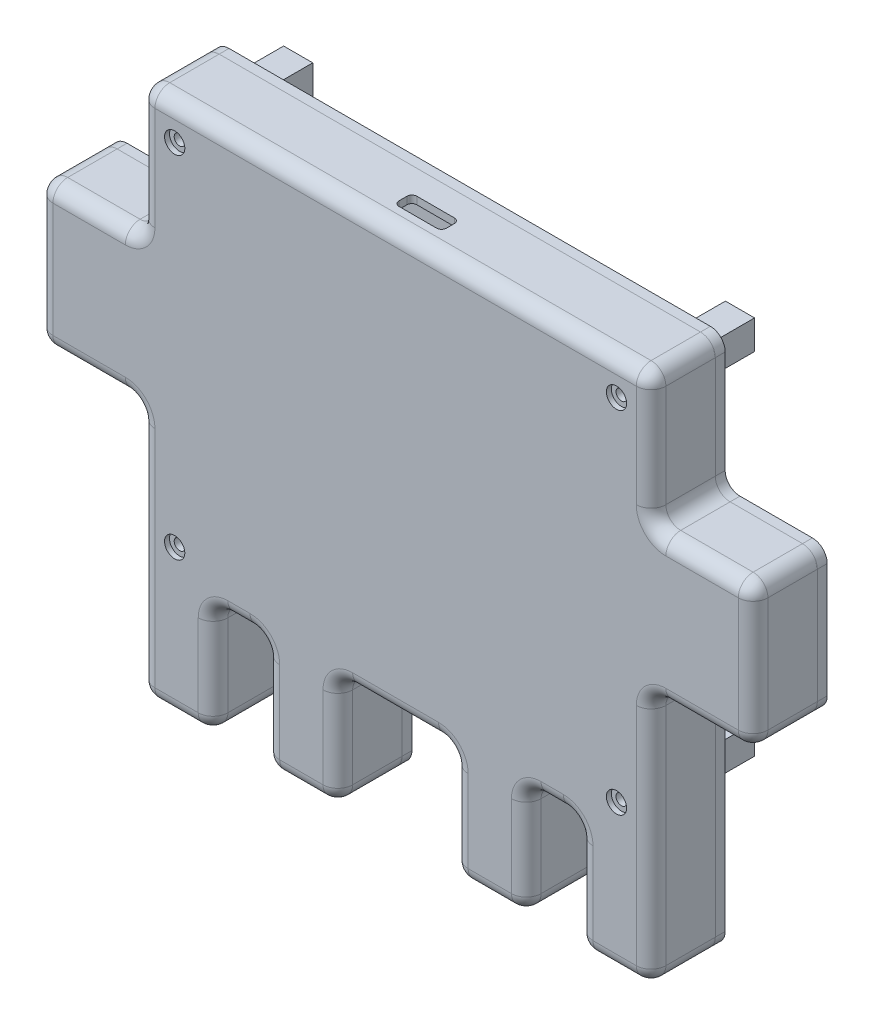
SolidWorks part; units mm, degrees
ref_plane "Front Plane" through (0, 0, 0) normal (0, 0, 1) x (1, 0, 0)
ref_plane "Top Plane" through (0, 0, 0) normal (0, 1, 0) x (1, 0, 0)
ref_plane "Right Plane" through (0, 0, 0) normal (1, 0, 0) x (0, 0, -1)
sketch "圖片" plane through (0, 0, 0) normal (0, 0, 1) x (1, 0, 0)
  line L0 (219.174, 501.4094) -> (1128.5073, 501.4094) construction
sketch "padTop" plane through (0, 0, 0) normal (0, 0, 1) x (1, 0, 0)
  line L0 (36.7115, 8.5135) -> (50.8115, 8.5135)
  line L1 (36.7115, 27.6135) -> (50.8115, 27.6135)
  line L2 (36.7115, 27.6135) -> (36.7115, 13.5135)
  line L3 (36.7115, 13.5135) -> (50.8115, 13.5135)
  line L4 (50.8115, 27.6135) -> (50.8115, 13.5135)
  line L5 (36.7115, 27.6135) -> (50.8115, 13.5135) construction
  line L6 (36.7115, 13.5135) -> (50.8115, 27.6135) construction
  line L7 (36.7115, 8.5135) -> (36.7115, -5.5865)
  line L8 (36.7115, -5.5865) -> (50.8115, -5.5865)
  line L9 (50.8115, 8.5135) -> (50.8115, -5.5865)
  line L10 (36.7115, 8.5135) -> (50.8115, -5.5865) construction
  line L11 (36.7115, -5.5865) -> (50.8115, 8.5135) construction
  line L12 (94.0115, 8.5135) -> (108.1115, 8.5135)
  line L13 (94.0115, 27.6135) -> (108.1115, 27.6135)
  line L14 (94.0115, 27.6135) -> (94.0115, 13.5135)
  line L15 (94.0115, 13.5135) -> (108.1115, 13.5135)
  line L16 (108.1115, 27.6135) -> (108.1115, 13.5135)
  line L17 (94.0115, 27.6135) -> (108.1115, 13.5135) construction
  line L18 (94.0115, 13.5135) -> (108.1115, 27.6135) construction
  line L19 (94.0115, 8.5135) -> (94.0115, -5.5865)
  line L20 (94.0115, -5.5865) -> (108.1115, -5.5865)
  line L21 (108.1115, 8.5135) -> (108.1115, -5.5865)
  line L22 (94.0115, 8.5135) -> (108.1115, -5.5865) construction
  line L23 (94.0115, -5.5865) -> (108.1115, 8.5135) construction
  line L24 (55.8115, 8.5135) -> (69.9115, 8.5135)
  line L25 (55.8115, 27.6135) -> (69.9115, 27.6135)
  line L26 (55.8115, 27.6135) -> (55.8115, 13.5135)
  line L27 (55.8115, 13.5135) -> (69.9115, 13.5135)
  line L28 (69.9115, 27.6135) -> (69.9115, 13.5135)
  line L29 (55.8115, 27.6135) -> (69.9115, 13.5135) construction
  line L30 (55.8115, 13.5135) -> (69.9115, 27.6135) construction
  line L31 (55.8115, 8.5135) -> (55.8115, -5.5865)
  line L32 (55.8115, -5.5865) -> (69.9115, -5.5865)
  line L33 (69.9115, 8.5135) -> (69.9115, -5.5865)
  line L34 (55.8115, 8.5135) -> (69.9115, -5.5865) construction
  line L35 (55.8115, -5.5865) -> (69.9115, 8.5135) construction
  line L36 (74.9115, 8.5135) -> (89.0115, 8.5135)
  line L37 (74.9115, 27.6135) -> (89.0115, 27.6135)
  line L38 (74.9115, 27.6135) -> (74.9115, 13.5135)
  line L39 (74.9115, 13.5135) -> (89.0115, 13.5135)
  line L40 (89.0115, 27.6135) -> (89.0115, 13.5135)
  line L41 (74.9115, 27.6135) -> (89.0115, 13.5135) construction
  line L42 (74.9115, 13.5135) -> (89.0115, 27.6135) construction
  line L43 (74.9115, 8.5135) -> (74.9115, -5.5865)
  line L44 (74.9115, -5.5865) -> (89.0115, -5.5865)
  line L45 (89.0115, 8.5135) -> (89.0115, -5.5865)
  line L46 (74.9115, 8.5135) -> (89.0115, -5.5865) construction
  line L47 (74.9115, -5.5865) -> (89.0115, 8.5135) construction
  line L48 (62.8615, 20.5635) -> (81.9615, 20.5635) construction
  line L49 (72.4115, 165.3189) -> (72.4115, -124.1918) construction
  line L50 (81.9615, 20.5635) -> (81.9615, 1.4635) construction
  line L51 (26.7144, 11.0135) -> (137.2086, 11.0135) construction
  line L52 (10.3648, 43.5052) -> (10.3648, 14.3095) construction
  line L53 (33.7615, 30.5635) -> (111.0615, 30.5635)
  line L54 (33.7615, 30.5635) -> (33.7615, -8.5365)
  line L55 (33.7615, -8.5365) -> (111.0615, -8.5365)
  line L56 (111.0615, 30.5635) -> (111.0615, -8.5365)
  line L57 (33.7615, 30.5635) -> (111.0615, -8.5365) construction
  line L58 (33.7615, -8.5365) -> (111.0615, 30.5635) construction
  line L59 (20.6927, 70.4526) -> (124.1303, 70.4526)
  line L60 (20.6927, 70.4526) -> (20.6927, -14.4886)
  line L61 (20.6927, -14.4886) -> (124.1303, -14.4886)
  line L62 (124.1303, 70.4526) -> (124.1303, -14.4886)
  line L63 (20.6927, 70.4526) -> (124.1303, -14.4886) construction
  line L64 (20.6927, -14.4886) -> (124.1303, 70.4526) construction
  line L65 (20.6927, 43.5052) -> (0.037, 43.5052)
  line L66 (20.6927, 43.5052) -> (20.6927, 14.3095)
  line L67 (20.6927, 14.3095) -> (0.037, 14.3095)
  line L68 (0.037, 43.5052) -> (0.037, 14.3095)
  line L69 (124.1303, 43.6826) -> (144.7861, 43.6826)
  line L70 (124.1303, 43.6826) -> (124.1303, 14.487)
  line L71 (124.1303, 14.487) -> (144.7861, 14.487)
  line L72 (144.7861, 43.6826) -> (144.7861, 14.487)
  line L73 (20.6927, -14.4886) -> (35.4563, -14.4886)
  line L74 (20.6927, -14.4886) -> (20.6927, -37.1354)
  line L75 (20.6927, -37.1354) -> (35.4563, -37.1354)
  line L76 (35.4563, -14.4886) -> (35.4563, -37.1354)
  line L77 (45.9563, -14.4886) -> (60.7199, -14.4886)
  line L78 (45.9563, -14.4886) -> (45.9563, -37.1354)
  line L79 (45.9563, -37.1354) -> (60.7199, -37.1354)
  line L80 (60.7199, -14.4886) -> (60.7199, -37.1354)
  line L81 (84.1032, -14.4886) -> (98.8668, -14.4886)
  line L82 (84.1032, -14.4886) -> (84.1032, -37.1354)
  line L83 (84.1032, -37.1354) -> (98.8668, -37.1354)
  line L84 (98.8668, -14.4886) -> (98.8668, -37.1354)
  line L85 (124.1303, -14.4886) -> (109.3668, -14.4886)
  line L86 (124.1303, -14.4886) -> (124.1303, -37.1354)
  line L87 (124.1303, -37.1354) -> (109.3668, -37.1354)
  line L88 (109.3668, -14.4886) -> (109.3668, -37.1354)
  line L89 (37.3633, 56.7764) -> (48.4633, 56.7764)
  line L90 (37.3633, 56.7764) -> (37.3633, 45.6764)
  line L91 (37.3633, 45.6764) -> (48.4633, 45.6764)
  line L92 (48.4633, 56.7764) -> (48.4633, 45.6764)
  line L93 (37.3633, 56.7764) -> (48.4633, 45.6764) construction
  line L94 (37.3633, 45.6764) -> (48.4633, 56.7764) construction
  line L95 (96.5235, 56.7764) -> (107.6235, 56.7764)
  line L96 (96.5235, 56.7764) -> (96.5235, 45.6764)
  line L97 (96.5235, 45.6764) -> (107.6235, 45.6764)
  line L98 (107.6235, 56.7764) -> (107.6235, 45.6764)
  line L99 (96.5235, 56.7764) -> (107.6235, 45.6764) construction
  line L100 (96.5235, 45.6764) -> (107.6235, 56.7764) construction
  line L105 (201129.9861, 29.0848) -> (-248870.0139, 29.0848) construction
  line L106 (122.9361, 36.1348) -> (137.0361, 36.1348)
  line L107 (-989.8311, 29.0848) -> (49010.1689, 29.0848) construction
  line L108 (139.9861, 38.7911) -> (119.9861, 38.7911)
  line L109 (139.9861, 38.7911) -> (139.9861, 19.3785)
  line L110 (139.9861, 19.3785) -> (119.9861, 19.3785)
  line L111 (119.9861, 38.7911) -> (119.9861, 19.3785)
  line L112 (139.9861, 38.7911) -> (119.9861, 19.3785) construction
  line L113 (139.9861, 19.3785) -> (119.9861, 38.7911) construction
  line L114 (43.7615, 20.5635) -> (62.8615, 20.5635) construction
  line L115 (32.9133, 61.2264) -> (52.9133, 61.2264)
  line L116 (32.9133, 61.2264) -> (32.9133, 41.2264)
  line L117 (32.9133, 41.2264) -> (52.9133, 41.2264)
  line L118 (52.9133, 61.2264) -> (52.9133, 41.2264)
  line L119 (32.9133, 61.2264) -> (52.9133, 41.2264) construction
  line L120 (32.9133, 41.2264) -> (52.9133, 61.2264) construction
  line L121 (92.0735, 61.2264) -> (112.0735, 61.2264)
  line L122 (92.0735, 61.2264) -> (92.0735, 41.2264)
  line L123 (92.0735, 41.2264) -> (112.0735, 41.2264)
  line L124 (112.0735, 61.2264) -> (112.0735, 41.2264)
  line L125 (92.0735, 61.2264) -> (112.0735, 41.2264) construction
  line L126 (92.0735, 41.2264) -> (112.0735, 61.2264) construction
  line L127 (81.9615, 20.5635) -> (101.0615, 20.5635) construction
  line L128 (53.3115, 20.5635) -> (53.3115, 3.2406) construction
  line L129 (91.5115, 20.5635) -> (91.5115, 3.2406) construction
  line L130 (124.1303, 43.6826) -> (144.7861, 43.6826) construction
  line L131 (20.6927, 43.5052) -> (0.037, 43.5052) construction
  line L132 (124.1303, 14.487) -> (144.7861, 14.487) construction
  line L133 (122.9361, 36.1348) -> (122.9361, 22.0348)
  line L134 (122.9361, 22.0348) -> (137.0361, 22.0348)
  line L135 (137.0361, 36.1348) -> (137.0361, 22.0348)
  line L136 (122.9361, 36.1348) -> (137.0361, 22.0348) construction
  line L137 (122.9361, 22.0348) -> (137.0361, 36.1348) construction
  circle A1 centre (14.837, 29.0848) radius 4.5
  point P0 (43.7615, 20.5635)
  point P5 (43.7615, 1.4635)
  point P10 (72.4115, 11.0135)
  point P11 (101.0615, 20.5635)
  point P16 (101.0615, 1.4635)
  point P21 (62.8615, 20.5635)
  point P26 (62.8615, 1.4635)
  point P31 (81.9615, 20.5635)
  point P36 (81.9615, 1.4635)
  point P45 (72.4115, 20.5635)
  point P46 (72.4115, 20.5635)
  point P50 (81.9615, 11.0135)
  point P51 (72.4115, 11.0135)
  point P56 (72.4115, 27.982)
  point P83 (42.9133, 51.2264)
  point P88 (102.0735, 51.2264)
  point P95 (129.9861, 29.0848)
  point P96 (129.9861, 29.0848)
  point P109 (124.7964, 29.0848)
  point P110 (102.0735, 51.2264)
  point P111 (42.9133, 51.2264)
  point P121 (129.9861, 29.0848)
  point P128 (53.3115, 11.0135)
  point P129 (91.5115, 11.0135)
  dimension "D8" = 10.5
  dimension "D16" = 14.1
  dimension "D13" = 9
  dimension "D1" = 14.1
  dimension "D2" = 19.1
  dimension "D3" = 19.1
  dimension "D4" = 19.1
  dimension "D5" = 19.1
  dimension "D6" = 10
  dimension "D7" = 10
  dimension "D9" = 10.5
  dimension "D10" = 11.1
  dimension "D11" = 14.8
  dimension "D12" = 20
  dimension "D14" = 14.8
  dimension "D15" = 20
  dimension "D17" = 103.4376
sketch "RP2024" plane through (0, 0, 0) normal (0, 0, 1) x (1, 0, 0)
  line L0 (20.6927, 70.4526) -> (124.1303, 70.4526) construction
  line L1 (60.8615, 68.7526) -> (83.9615, 68.7526) construction
  line L2 (60.8615, 68.7526) -> (60.8615, 15.2526) construction
  line L3 (60.8615, 15.2526) -> (83.9615, 15.2526) construction
  line L4 (83.9615, 68.7526) -> (83.9615, 15.2526) construction
  line L5 (60.8615, 68.7526) -> (83.9615, 15.2526) construction
  line L6 (60.8615, 15.2526) -> (83.9615, 68.7526) construction
  line L7 (72.4115, 165.3189) -> (72.4115, -124.1918) construction
  point P0 (72.4115, 42.0026)
  dimension "D1" = 53.5
  dimension "D2" = 23.1
  dimension "D3" = 1.7
sketch "numb" plane through (0, 0, 0) normal (0, 0, 1) x (1, 0, 0)
  circle A1 centre (14.837, 29.0848) radius 17.5
  dimension "D2" = 35
extrude "填料-伸長1" add sketch "padTop" along normal blind 3 contours L109 L110 L66 L60 L61 L62 L59 L108 L115 L118 L117 L116 L53 L56 L55 L54 L121 L124 L123 L122 | L72 L69 L62 L71 | L111 L108 L60 L65 L68 L67 L66 L110 | L124 L121 L122 L123 L95 L98 L97 L96 | L118 L115 L116 L117 L89 L92 L91 L90 | L74 L73 L76 L75 | L78 L77 L80 L79 | L82 L81 L84 L83 | L86 L85 L88 L87 region at (71.5802, 34.6583, 0) region at (9.8374, 28.8864, 0) region at (134.4582, 43.325, 0) region at (42.9133, 60.9435, 0) region at (102.0735, 60.9435, 0)
extrude "填料-伸長4" add sketch "padTop<8>" against normal blind 2 contours L109 L110 L66 L60 L61 L62 L59 L108 L115 L118 L117 L116 L53 L56 L55 L54 L121 L124 L123 L122 | L72 L69 L62 L71 | L111 L108 L60 L65 L68 L67 L66 L110 | L76 L61 L74 L75 | L80 L61 L78 L79 | L84 L61 L82 L83 | L61 L88 L87 L86 | L56 L53 L54 L55 L1 L4 L3 L2 L0 L9 L8 L7 L13 L16 L15 L14 L12 L21 L20 L19 L25 L28 L27 L26 L24 L33 L32 L31 L37 L40 L39 L38 L36 L45 L44 L43 | L133 L134 L66 L106 | L110 L111 L108 L109 region at (72.4115, 11.0135, 0) region at (71.5802, 34.6583, 0) region at (9.8374, 28.8864, 0) region at (134.4582, 43.325, 0) region at (28.0745, -25.812, 0) region at (123.5332, 29.0848, 0) region at (53.3381, -25.812, 0) region at (116.7485, -25.812, 0) region at (91.485, -25.812, 0)
sketch "padTop<8>" plane through (0, 0, 0) normal (0, 0, 1) x (1, 0, 0) same geometry as "padTop"
sketch "草圖2" plane through (0, 0, 0) normal (0, 0, 1) x (1, 0, 0)
  line L0 (20.6927, 43.5052) -> (0.037, 43.5052)
  line L5 (0.037, 43.5052) -> (0.037, 14.3095)
  line L6 (0.037, 14.3095) -> (20.6927, 14.3095)
  line L31 (20.6927, 14.3095) -> (20.6927, -37.1354)
  line L32 (20.6927, -37.1354) -> (35.4563, -37.1354)
  line L33 (35.4563, -37.1354) -> (35.4563, -14.4886)
  line L34 (35.4563, -14.4886) -> (45.9563, -14.4886)
  line L35 (45.9563, -14.4886) -> (45.9563, -37.1354)
  line L36 (45.9563, -37.1354) -> (60.7199, -37.1354)
  line L37 (60.7199, -37.1354) -> (60.7199, -14.4886)
  line L38 (60.7199, -14.4886) -> (84.1032, -14.4886)
  line L39 (84.1032, -14.4886) -> (84.1032, -37.1354)
  line L40 (84.1032, -37.1354) -> (98.8668, -37.1354)
  line L41 (98.8668, -37.1354) -> (98.8668, -14.4886)
  line L42 (98.8668, -14.4886) -> (109.3668, -14.4886)
  line L43 (109.3668, -14.4886) -> (109.3668, -37.1354)
  line L44 (109.3668, -37.1354) -> (124.1303, -37.1354)
  line L45 (124.1303, -37.1354) -> (124.1303, 14.487)
  line L46 (124.1303, 14.487) -> (144.7861, 14.487)
  line L47 (144.7861, 14.487) -> (144.7861, 43.6826)
  line L48 (144.7861, 43.6826) -> (124.1303, 43.6826)
  line L49 (124.1303, 43.6826) -> (124.1303, 70.4526)
  line L50 (124.1303, 70.4526) -> (20.6927, 70.4526)
  line L51 (20.6927, 70.4526) -> (20.6927, 43.5052)
extrude "填料-伸長6" add sketch "草圖2" along normal blind 13 separate body
fillet "圓角2" radius 3 48 edges at (72.4115, 70.4526, 13) (124.1303, 57.0676, 13) (134.4582, 43.6826, 13) (144.7861, 29.0848, 13) (134.4582, 14.487, 13) (124.1303, -11.3242, 13) (116.7485, -37.1354, 13) (109.3668, -25.812, 13) (104.1168, -14.4886, 13) (98.8668, -25.812, 13) (91.485, -37.1354, 13) (84.1032, -25.812, 13) (72.4115, -14.4886, 13) (60.7199, -25.812, 13) (53.3381, -37.1354, 13) (45.9563, -25.812, 13) (40.7063, -14.4886, 13) (35.4563, -25.812, 13) (28.0745, -37.1354, 13) (20.6927, -11.4129, 13) (10.3648, 14.3095, 13) (0.037, 28.9073, 13) (10.3648, 43.5052, 13) (20.6927, 56.9789, 13) (20.6927, 70.4526, 6.5) (20.6927, 43.5052, 6.5) (0.037, 43.5052, 6.5) (35.4563, -14.4886, 6.5) (35.4563, -37.1354, 6.5) (0.037, 14.3095, 6.5) (20.6927, 14.3095, 6.5) (20.6927, -37.1354, 6.5) (45.9563, -14.4886, 6.5) (45.9563, -37.1354, 6.5) (60.7199, -37.1354, 6.5) (60.7199, -14.4886, 6.5) (98.8668, -14.4886, 6.5) (98.8668, -37.1354, 6.5) (84.1032, -37.1354, 6.5) (84.1032, -14.4886, 6.5) (109.3668, -14.4886, 6.5) (109.3668, -37.1354, 6.5) (124.1303, -37.1354, 6.5) (124.1303, 14.487, 6.5) (144.7861, 14.487, 6.5) (144.7861, 43.6826, 6.5) (124.1303, 43.6826, 6.5) (124.1303, 70.4526, 6.5)
shell "薄殼1" thickness 1.5 removed face at (72.4115, -0.4642, 0)
fillet "圓角4" radius 3 47 edges at (20.6927, -11.4129, 3) (10.3648, 14.3095, 3) (40.7063, -14.4886, 3) (124.1303, 57.0676, 3) (20.6927, 70.4526, 0.5) (0.037, 43.5052, 0.5) (10.3648, 43.5052, 3) (20.6927, 43.5052, 0.5) (0.037, 28.9073, 3) (0.037, 14.3095, 0.5) (20.6927, 14.3095, 0.5) (20.6927, -37.1354, 0.5) (35.4563, -37.1354, 0.5) (28.0745, -37.1354, 3) (35.4563, -25.812, 3) (45.9563, -14.4886, 0.5) (72.4115, 70.4526, 3) (124.1303, 70.4526, 0.5) (124.1303, 43.6826, 0.5) (134.4582, 43.6826, 3) (144.7861, 43.6826, 0.5) (144.7861, 29.0848, 3) (144.7861, 14.487, 0.5) (124.1303, 14.487, 0.5) (124.1303, -37.1354, 0.5) (109.3668, -37.1354, 0.5) (98.8668, -14.4886, 0.5) (84.1032, -37.1354, 0.5) (98.8668, -37.1354, 0.5) (109.3668, -14.4886, 0.5) (134.4582, 14.487, 3) (109.3668, -25.812, 3) (116.7485, -37.1354, 3) (124.1303, -11.3242, 3) (104.1168, -14.4886, 3) (98.8668, -25.812, 3) (91.485, -37.1354, 3) (84.1032, -14.4886, 0.5) (60.7199, -14.4886, 0.5) (53.3381, -37.1354, 3) (45.9563, -25.812, 3) (60.7199, -25.812, 3) (84.1032, -25.812, 3) (72.4115, -14.4886, 3) (35.4563, -14.4886, 0.5) (45.9563, -37.1354, 0.5) (60.7199, -37.1354, 0.5)
ref_plane "平面1" through (0, 0, 11.5) normal (0, 0, -1) x (-1, 0, 0)
sketch "草圖4" plane through (0, 0, 11.5) normal (0, 0, -1) x (-1, 0, 0)
  line L0 (-92.5115, 16.0135) -> (-90.5115, 16.0135)
  line L1 (-54.3115, 16.0135) -> (-52.3115, 16.0135)
  line L4 (-54.3115, 16.0135) -> (-54.3115, 6.0135)
  line L5 (-54.3115, 6.0135) -> (-52.3115, 6.0135)
  line L6 (-52.3115, 16.0135) -> (-52.3115, 6.0135)
  line L7 (-54.3115, 16.0135) -> (-52.3115, 6.0135) construction
  line L8 (-54.3115, 6.0135) -> (-52.3115, 16.0135) construction
  line L9 (-58.3115, 12.0135) -> (-48.3115, 12.0135)
  line L10 (-58.3115, 12.0135) -> (-58.3115, 10.0135)
  line L11 (-58.3115, 10.0135) -> (-48.3115, 10.0135)
  line L12 (-48.3115, 12.0135) -> (-48.3115, 10.0135)
  line L13 (-58.3115, 12.0135) -> (-48.3115, 10.0135) construction
  line L14 (-58.3115, 10.0135) -> (-48.3115, 12.0135) construction
  line L15 (-92.5115, 16.0135) -> (-92.5115, 6.0135)
  line L16 (-92.5115, 6.0135) -> (-90.5115, 6.0135)
  line L17 (-90.5115, 16.0135) -> (-90.5115, 6.0135)
  line L18 (-92.5115, 16.0135) -> (-90.5115, 6.0135) construction
  line L19 (-92.5115, 6.0135) -> (-90.5115, 16.0135) construction
  line L20 (-96.5115, 12.0135) -> (-86.5115, 12.0135)
  line L21 (-96.5115, 12.0135) -> (-96.5115, 10.0135)
  line L22 (-96.5115, 10.0135) -> (-86.5115, 10.0135)
  line L23 (-86.5115, 12.0135) -> (-86.5115, 10.0135)
  line L24 (-96.5115, 12.0135) -> (-86.5115, 10.0135) construction
  line L25 (-96.5115, 10.0135) -> (-86.5115, 12.0135) construction
  point P0 (-53.3115, 11.0135)
  point P5 (-53.3115, 11.0135)
  point P11 (-91.5115, 11.0135)
  point P17 (-91.5115, 11.0135)
  dimension "D1" = 10
  dimension "D2" = 2
ref_plane "平面2" through (0, 0, -2) normal (0, 0, 1) x (1, 0, 0)
sketch "草圖5" plane through (0, 0, -2) normal (0, 0, 1) x (1, 0, 0)
  line L1 (26.7427, 64.4026) -> (28.6427, 64.4026)
  line L2 (26.7427, 64.4026) -> (26.7427, 62.5026)
  line L3 (26.7427, 62.5026) -> (28.6427, 62.5026)
  line L4 (28.6427, 64.4026) -> (28.6427, 62.5026)
  line L5 (26.7427, 64.4026) -> (28.6427, 62.5026) construction
  line L6 (26.7427, 62.5026) -> (28.6427, 64.4026) construction
  line L7 (20.6927, 70.4526) -> (20.6927, -14.4886) construction
  line L8 (26.7427, -6.5386) -> (28.6427, -6.5386)
  line L9 (24.7427, 66.4026) -> (30.6427, 66.4026)
  line L10 (24.7427, 66.4026) -> (24.7427, 60.5026)
  line L11 (24.7427, 60.5026) -> (30.6427, 60.5026)
  line L12 (30.6427, 66.4026) -> (30.6427, 60.5026)
  line L13 (24.7427, 66.4026) -> (30.6427, 60.5026) construction
  line L14 (24.7427, 60.5026) -> (30.6427, 66.4026) construction
  line L15 (26.7427, -6.5386) -> (26.7427, -8.4386)
  line L16 (26.7427, -8.4386) -> (28.6427, -8.4386)
  line L17 (28.6427, -6.5386) -> (28.6427, -8.4386)
  line L18 (26.7427, -6.5386) -> (28.6427, -8.4386) construction
  line L19 (26.7427, -8.4386) -> (28.6427, -6.5386) construction
  line L20 (24.7427, -4.5386) -> (30.6427, -4.5386)
  line L21 (24.7427, -4.5386) -> (24.7427, -10.4386)
  line L22 (24.7427, -10.4386) -> (30.6427, -10.4386)
  line L23 (30.6427, -4.5386) -> (30.6427, -10.4386)
  line L24 (24.7427, -4.5386) -> (30.6427, -10.4386) construction
  line L25 (24.7427, -10.4386) -> (30.6427, -4.5386) construction
  line L26 (116.1803, -6.5386) -> (118.0803, -6.5386)
  line L27 (116.1803, -6.5386) -> (116.1803, -8.4386)
  line L28 (116.1803, -8.4386) -> (118.0803, -8.4386)
  line L29 (118.0803, -6.5386) -> (118.0803, -8.4386)
  line L30 (116.1803, -6.5386) -> (118.0803, -8.4386) construction
  line L31 (116.1803, -8.4386) -> (118.0803, -6.5386) construction
  line L32 (114.1803, -4.5386) -> (120.0803, -4.5386)
  line L33 (114.1803, -4.5386) -> (114.1803, -10.4386)
  line L34 (114.1803, -10.4386) -> (120.0803, -10.4386)
  line L35 (120.0803, -4.5386) -> (120.0803, -10.4386)
  line L36 (114.1803, -4.5386) -> (120.0803, -10.4386) construction
  line L37 (114.1803, -10.4386) -> (120.0803, -4.5386) construction
  line L38 (116.1803, 64.4026) -> (118.0803, 64.4026)
  line L39 (116.1803, 64.4026) -> (116.1803, 62.5026)
  line L40 (116.1803, 62.5026) -> (118.0803, 62.5026)
  line L41 (118.0803, 64.4026) -> (118.0803, 62.5026)
  line L42 (116.1803, 64.4026) -> (118.0803, 62.5026) construction
  line L43 (116.1803, 62.5026) -> (118.0803, 64.4026) construction
  line L44 (114.1803, 66.4026) -> (120.0803, 66.4026)
  line L45 (114.1803, 66.4026) -> (114.1803, 60.5026)
  line L46 (114.1803, 60.5026) -> (120.0803, 60.5026)
  line L47 (120.0803, 66.4026) -> (120.0803, 60.5026)
  line L48 (114.1803, 66.4026) -> (120.0803, 60.5026) construction
  line L49 (114.1803, 60.5026) -> (120.0803, 66.4026) construction
  line L50 (52.3115, 16.0135) -> (54.3115, 16.0135)
  line L51 (20.6927, 70.4526) -> (124.1303, 70.4526) construction
  line L52 (20.6927, -14.4886) -> (124.1303, -14.4886) construction
  line L53 (124.1303, 70.4526) -> (124.1303, -14.4886) construction
  line L54 (52.3115, 16.0135) -> (52.3115, 6.0135)
  line L55 (52.3115, 6.0135) -> (54.3115, 6.0135)
  line L56 (54.3115, 16.0135) -> (54.3115, 6.0135)
  line L57 (48.3115, 12.0135) -> (58.3115, 12.0135)
  line L58 (48.3115, 12.0135) -> (48.3115, 10.0135)
  line L59 (48.3115, 10.0135) -> (58.3115, 10.0135)
  line L60 (58.3115, 12.0135) -> (58.3115, 10.0135)
  line L61 (86.5115, 12.0135) -> (96.5115, 12.0135)
  line L62 (86.5115, 12.0135) -> (86.5115, 10.0135)
  line L63 (86.5115, 10.0135) -> (96.5115, 10.0135)
  line L64 (96.5115, 12.0135) -> (96.5115, 10.0135)
  line L65 (92.5115, 16.0135) -> (90.5115, 16.0135)
  line L66 (92.5115, 16.0135) -> (92.5115, 6.0135)
  line L67 (92.5115, 6.0135) -> (90.5115, 6.0135)
  line L68 (90.5115, 16.0135) -> (90.5115, 6.0135)
  point P0 (27.6927, 63.4526)
  point P5 (27.6927, 63.4526)
  point P14 (27.6927, -7.4886)
  point P19 (27.6927, -7.4886)
  point P24 (117.1303, -7.4886)
  point P29 (117.1303, -7.4886)
  point P34 (117.1303, 63.4526)
  point P39 (117.1303, 63.4526)
  dimension "D1" = 1.9
  dimension "D2" = 7
  dimension "D3" = 7
  dimension "D4" = 5.9
  dimension "D5" = 7
  dimension "D6" = 7
extrude "填料-伸長9" add sketch "草圖5" against normal blind 10 contours L61 L68 L63 L66 | L68 L61 L62 L63 | L65 L68 L61 L66 | L63 L68 L67 L66 | L61 L66 L63 L64 | L54 L59 L56 L57 | L58 L59 L54 L57 | L54 L57 L56 L50 | L60 L57 L56 L59 | L59 L54 L55 L56 | L23 L20 L21 L22 L8 L17 L16 L15 | L35 L32 L33 L34 L26 L29 L28 L27 | L47 L44 L45 L46 L38 L41 L40 L39 | L12 L9 L10 L11 L1 L4 L3 L2 region at (27.6927, 66.3191, -2) region at (27.6927, -4.622, -2) region at (117.1303, -4.622, -2) region at (117.1303, 66.3191, -2) region at (53.3115, 14.0135, -2) region at (53.3115, 11.0135, -2) region at (50.3115, 11.0135, -2) region at (56.3115, 11.0135, -2) region at (53.3115, 8.0135, -2) region at (88.5115, 11.0135, -2) region at (91.5115, 14.0135, -2) region at (91.5115, 11.0135, -2) region at (94.5115, 11.0135, -2) region at (91.5115, 8.0135, -2)
ref_plane "平面3" through (0, 0, 13) normal (0, 0, 1) x (1, 0, 0)
sketch "草圖7" plane through (0, 0, 13) normal (0, 0, 1) x (1, 0, 0)
  line L0 (26.7427, -6.5386) -> (28.6427, -8.4386) construction
  circle A0 centre (27.6927, 63.4526) radius 2.05
  circle A1 centre (117.1303, 63.4526) radius 2.05
  circle A2 centre (117.1303, -7.4886) radius 2.05
  circle A3 centre (27.6927, -7.4886) radius 2.05
  circle A4 centre (27.6927, 63.4526) radius 1.1
  circle A5 centre (117.1303, 63.4526) radius 1.1
  circle A6 centre (117.1303, -7.4886) radius 1.1
  circle A7 centre (27.6927, -7.4886) radius 1.1
  dimension "D1" = 4.1
  dimension "D2" = 2.2
extrude "除料-伸長1" cut sketch "草圖7" against normal up to next (1.5 mm away) contours A6 | A4 | A5 | A7
extrude "除料-伸長2" cut sketch "草圖7<4>" against normal blind 1
sketch "草圖7<4>" plane through (0, 0, 13) normal (0, 0, 1) x (1, 0, 0) same geometry as "草圖7"
ref_plane "平面4" through (0, 70.4526, 0) normal (0, 1, 0) x (1, 0, 0)
sketch "草圖10" plane through (0, 70.4526, 0) normal (0, 1, 0) x (1, 0, 0)
  line L0 (72.4115, 0) -> (72.4115, -13) construction
  line L1 (-55.8734, -13) -> (55.8734, -13) construction
  line L7 (67.6115, -4.9) -> (77.2115, -4.9)
  line L8 (67.6115, -4.9) -> (67.6115, -8.5)
  line L9 (67.6115, -8.5) -> (77.2115, -8.5)
  line L10 (77.2115, -4.9) -> (77.2115, -8.5)
  line L11 (67.6115, -4.9) -> (77.2115, -8.5) construction
  line L12 (67.6115, -8.5) -> (77.2115, -4.9) construction
  point P5 (72.4115, -6.7)
  dimension "D1" = 3.6
  dimension "D2" = 9.6
  dimension "D3" = 4.5
extrude "除料-伸長3" cut sketch "草圖10" against normal up to next (1.5 mm away)
fillet "圓角5" radius 1 4 edges at (67.6115, 69.7026, 4.9) (67.6115, 69.7026, 8.5) (77.2115, 69.7026, 4.9) (77.2115, 69.7026, 8.5)
ref_plane "平面5" through (0, 0, 11.5) normal (0, 0, -1) x (-1, 0, 0)
sketch "草圖12" plane through (0, 0, 11.5) normal (0, 0, -1) x (-1, 0, 0)
  line L0 (-60.8615, 68.7526) -> (-60.8615, 15.2526) construction
  line L1 (-60.6615, 68.9526) -> (-59.6615, 68.9526)
  line L2 (-60.6615, 68.9526) -> (-60.6615, 63.9526)
  line L3 (-60.6615, 63.9526) -> (-59.6615, 63.9526)
  line L4 (-59.6615, 68.9526) -> (-59.6615, 63.9526)
  line L5 (-60.6615, 68.9526) -> (-59.6615, 63.9526) construction
  line L6 (-60.6615, 63.9526) -> (-59.6615, 68.9526) construction
  line L7 (-85.1615, 68.9526) -> (-84.1615, 68.9526)
  line L8 (-85.1615, 68.9526) -> (-85.1615, 63.9526)
  line L9 (-85.1615, 63.9526) -> (-84.1615, 63.9526)
  line L10 (-84.1615, 68.9526) -> (-84.1615, 63.9526)
  line L11 (-85.1615, 68.9526) -> (-84.1615, 63.9526) construction
  line L12 (-85.1615, 63.9526) -> (-84.1615, 68.9526) construction
  line L13 (-20.6927, 70.4526) -> (-124.1303, 70.4526) construction
  line L14 (-83.9615, 68.7526) -> (-83.9615, 15.2526) construction
  line L15 (-85.1615, 15.0526) -> (-80.1615, 15.0526)
  line L16 (-60.6615, 14.0526) -> (-59.6615, 14.0526)
  line L17 (-60.6615, 14.0526) -> (-60.6615, 19.0526)
  line L18 (-60.6615, 19.0526) -> (-59.6615, 19.0526)
  line L19 (-59.6615, 14.0526) -> (-59.6615, 19.0526)
  line L20 (-60.6615, 14.0526) -> (-59.6615, 19.0526) construction
  line L21 (-60.6615, 19.0526) -> (-59.6615, 14.0526) construction
  line L22 (-64.6615, 15.0526) -> (-59.6615, 15.0526)
  line L23 (-64.6615, 15.0526) -> (-64.6615, 14.0526)
  line L24 (-64.6615, 14.0526) -> (-59.6615, 14.0526)
  line L25 (-59.6615, 15.0526) -> (-59.6615, 14.0526)
  line L26 (-64.6615, 15.0526) -> (-59.6615, 14.0526) construction
  line L27 (-64.6615, 14.0526) -> (-59.6615, 15.0526) construction
  line L28 (-85.1615, 19.0526) -> (-84.1615, 19.0526)
  line L29 (-85.1615, 19.0526) -> (-85.1615, 14.0526)
  line L30 (-85.1615, 14.0526) -> (-84.1615, 14.0526)
  line L31 (-84.1615, 19.0526) -> (-84.1615, 14.0526)
  line L32 (-85.1615, 19.0526) -> (-84.1615, 14.0526) construction
  line L33 (-85.1615, 14.0526) -> (-84.1615, 19.0526) construction
  line L34 (-85.1615, 15.0526) -> (-85.1615, 14.0526)
  line L35 (-85.1615, 14.0526) -> (-80.1615, 14.0526)
  line L36 (-80.1615, 15.0526) -> (-80.1615, 14.0526)
  line L37 (-85.1615, 15.0526) -> (-80.1615, 14.0526) construction
  line L38 (-85.1615, 14.0526) -> (-80.1615, 15.0526) construction
  line L39 (-60.8615, 15.2526) -> (-83.9615, 15.2526) construction
  point P0 (-60.1615, 66.4526)
  point P5 (-84.6615, 66.4526)
  point P12 (-60.1615, 68.9526)
  point P17 (-62.1615, 14.5526)
  point P18 (-60.1615, 16.5526)
  point P27 (-84.6615, 16.5526)
  point P32 (-82.6615, 14.5526)
  dimension "D1" = 1
  dimension "D2" = 5
  dimension "D3" = 0.2
  dimension "D4" = 1.5
  dimension "D5" = 0.2
  dimension "D6" = 0.2
extrude "填料-伸長10" add sketch "草圖12" along normal blind 5 contours L31 L28 L29 L15 | L36 L15 L31 L35 | L31 L15 L29 L30 | L23 L24 L17 L22 | L22 L17 L16 L19 | L17 L22 L19 L18 | L4 L1 L2 L3 | L10 L7 L8 L9
sketch "草圖15" plane through (0, 0, 11.5) normal (0, 0, -1) x (-1, 0, 0)
  circle A0 centre (-27.6927, -7.4886) radius 1.1
  circle A1 centre (-27.6927, -7.4886) radius 3
  circle A2 centre (-27.6927, 63.4526) radius 1.1
  circle A3 centre (-27.6927, 63.4526) radius 3
  circle A4 centre (-117.1303, 63.4526) radius 1.1
  circle A5 centre (-117.1303, 63.4526) radius 3
  circle A6 centre (-117.1303, -7.4886) radius 3
  circle A7 centre (-117.1303, -7.4886) radius 1.1
  dimension "D1" = 6
extrude "填料-伸長11" add sketch "草圖15" along normal blind 1
chamfer "導角1" distance 1.5 angle 74 4 edges at (85.1615, 16.5526, 11.5) (82.6615, 14.0526, 11.5) (62.1615, 14.0526, 11.5) (59.6615, 16.5526, 11.5) first distance on face at (114.1303, 63.4526, 11.5)
